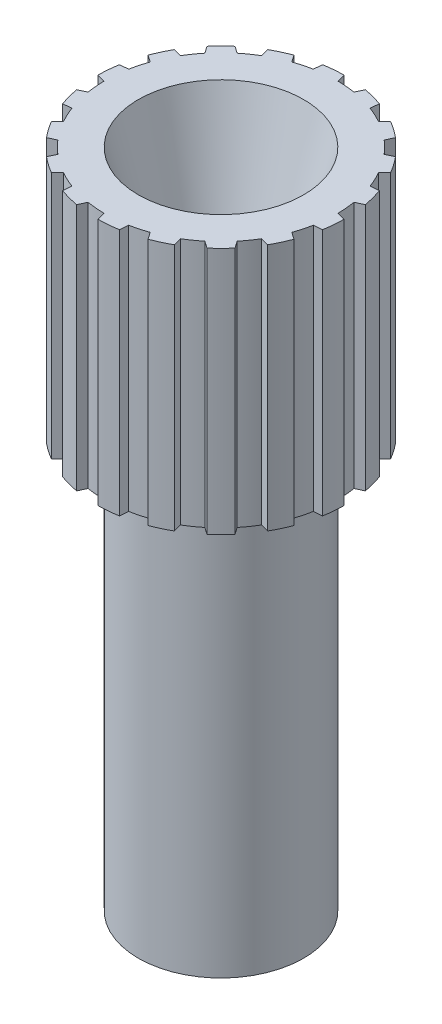
SolidWorks part; units mm, degrees
ref_plane "Front Plane" through (0, 0, 0) normal (0, 0, 1) x (1, 0, 0)
ref_plane "Top Plane" through (0, 0, 0) normal (0, 1, 0) x (1, 0, 0)
ref_plane "Right Plane" through (0, 0, 0) normal (1, 0, 0) x (0, 0, -1)
sketch "Sketch1" plane through (0, 0, 0) normal (0, 1, 0) x (1, 0, 0)
  circle A0 centre (0, 0) radius 5
  circle A1 centre (0, 0) radius 7.5
  dimension "D1" = 15
  dimension "D2" = 10
extrude "Boss-Extrude1" add sketch "Sketch1" along normal blind 15 contours A1
extrude "Boss-Extrude2" add sketch "Sketch1<3>" against normal blind 25 contours A0
sketch "Sketch1<3>" plane through (0, 0, 0) normal (0, 1, 0) x (1, 0, 0) same geometry as "Sketch1"
sketch "Sketch2" plane through (0, 15, 0) normal (0, 1, 0) x (1, 0, 0)
  line L0 (0, 7.3) -> (0, 0) construction
  line L1 (0, 0) -> (1.2676, 7.1891) construction
  line L4 (1.5729, 7.8438) -> (1.1362, 6.9072)
  line L5 (-0.187, 7.9978) -> (0.0805, 6.9995)
  arc A0 (1.1362, 6.9072) -> (0.0805, 6.9995) centre (0, 0) ccw
  arc A1 (1.5729, 7.8438) -> (-0.187, 7.9978) centre (0, 0) ccw
  arc A2 (1.2676, 7.1891) -> (0, 7.3) centre (0, 0) ccw construction
  dimension "D1" = 16
  dimension "D2" = 7
  dimension "D3" = 14.6
  dimension "D4" = 15
  dimension "D5" = 15
  dimension "D6" = 10
extrude "Cut-Extrude1" cut sketch "Sketch2" against normal through all
sketch "Sketch3" plane through (0, 15, 0) normal (0, 1, 0) x (1, 0, 0)
  circle A0 centre (0, 0) radius 5
  dimension "D1" = 10
extrude "Cut-Extrude2" cut sketch "Sketch3" against normal blind 15 draft 15
pattern_circular "CirPattern1" count 18 over 360 about axis through (0, 15, 0) along (0, 1, 0) of "Cut-Extrude1"
